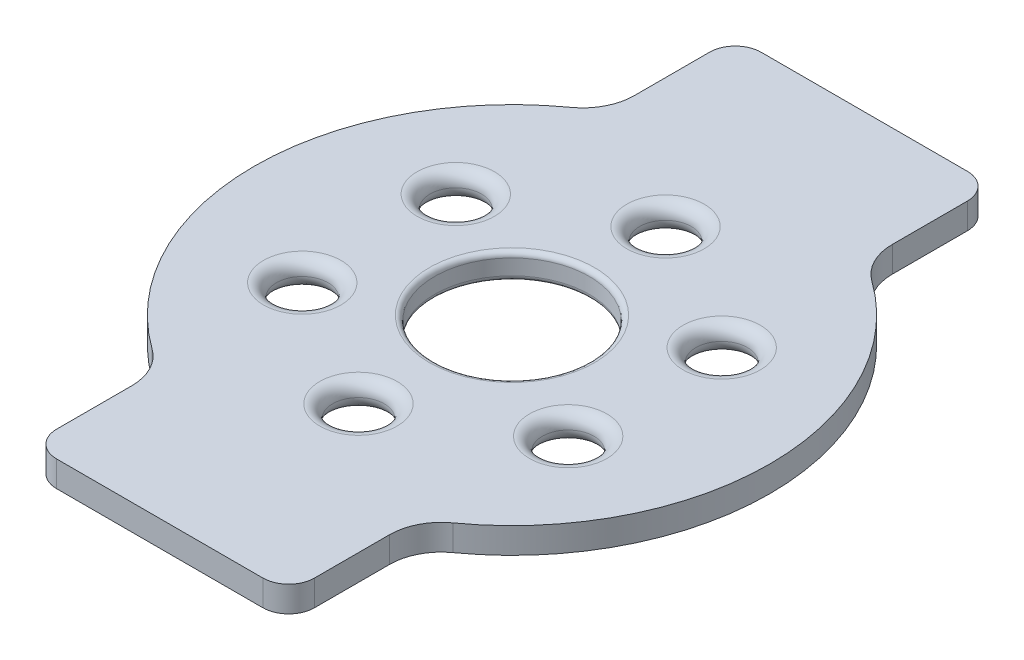
SolidWorks part; units mm, degrees
material "Titânio"
ref_plane "Plano frontal" through (0, 0, 0) normal (0, 0, 1) x (1, 0, 0)
ref_plane "Plano superior" through (0, 0, 0) normal (0, 1, 0) x (1, 0, 0)
ref_plane "Plano direito" through (0, 0, 0) normal (1, 0, 0) x (0, 0, -1)
sketch "Esboço1" plane through (0, 0, 0) normal (0, 1, 0) x (1, 0, 0)
  line L0 (0, 100) -> (0, 136.6025) construction
  line L1 (-50, 136.6025) -> (50, 136.6025)
  line L3 (-50, 86.6025) -> (-50, 136.6025)
  line L4 (50, 86.6025) -> (50, 136.6025)
  line L5 (0, 0) -> (-123.3378, 0) construction
  line L6 (50, -86.6025) -> (50, -136.6025)
  line L7 (-50, -136.6025) -> (50, -136.6025)
  line L8 (-50, -86.6025) -> (-50, -136.6025)
  arc A0 (-50, 86.6025) -> (-50, -86.6025) centre (0, 0) ccw
  arc A1 (50, -86.6025) -> (50, 86.6025) centre (0, 0) ccw
  circle A2 centre (0, 0) radius 30
  point P14 (-100, 0)
  point P15 (100, 0)
  dimension "D1" = 200
  dimension "D4" = 273.2051
  dimension "D2" = 50
  dimension "D3" = 50
  dimension "D5" = 200
extrude "Ressalto-extrusão1" add sketch "Esboço1" along normal blind 10
fillet "Filete1" radius 20 4 edges at (50, 5, -86.6025) (-50, 5, -86.6025) (-50, 5, 86.6025) (50, 5, 86.6025)
fillet "Filete2" radius 2 2 edges at (0, 10, 30) (0, 0, 30)
fillet "Filete3" radius 10 2 edges at (-50, 5, 136.6025) (50, 5, 136.6025)
fillet "Filete4" radius 10 2 edges at (50, 5, -136.6025) (-50, 5, -136.6025)
sketch "Esboço2" plane through (0, 10, 0) normal (0, 1, 0) x (1, 0, 0)
  line L0 (0, 0) -> (0, 59.54) construction
  line L1 (0, 0) -> (51.5632, 29.77) construction
  circle A0 centre (0, 59.54) radius 10
  circle A1 centre (51.5632, 29.77) radius 10
  circle A2 centre (51.5632, -29.77) radius 10
  circle A3 centre (0, -59.54) radius 10
  circle A4 centre (-51.5632, -29.77) radius 10
  circle A5 centre (-51.5632, 29.77) radius 10
  dimension "D1" = 6
  dimension "D2" = 60
extrude "Corte-extrusão1" cut sketch "Esboço2" against normal through all
fillet "Filete5" radius 5 12 edges at (51.5632, 0, 39.77) (51.5632, 10, 39.77) (51.5632, 0, -19.77) (51.5632, 10, -19.77) (0, 0, 69.54) (0, 10, 69.54) (0, 0, -49.54) (0, 10, -49.54) (-51.5632, 0, 39.77) (-51.5632, 10, 39.77) (-51.5632, 0, -19.77) (-51.5632, 10, -19.77)
